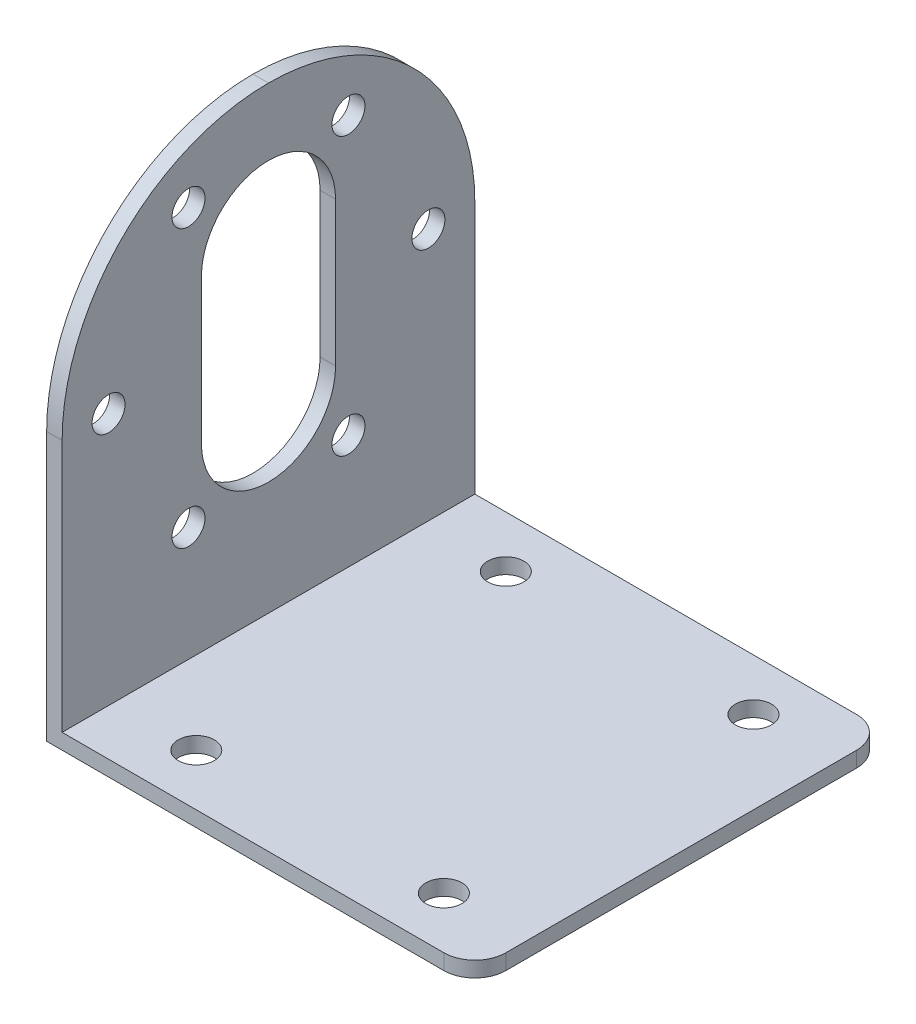
SolidWorks part; units mm, degrees
ref_plane "Front" through (0, 0, 0) normal (0, 0, 1) x (1, 0, 0)
ref_plane "Top" through (0, 0, 0) normal (0, 1, 0) x (1, 0, 0)
ref_plane "Right" through (0, 0, 0) normal (1, 0, 0) x (0, 0, -1)
sketch "草图3" plane through (0, 0, 0) normal (0, 1, 0) x (1, 0, 0)
  line L1 (-20.75, -20) -> (20.75, -20)
  line L2 (-20.75, -20) -> (-20.75, 20)
  line L3 (-20.75, 20) -> (20.75, 20)
  line L4 (20.75, -20) -> (20.75, 20)
  line L5 (-20.75, -20) -> (20.75, 20) construction
  line L6 (-20.75, 20) -> (20.75, -20) construction
  point P0 (0, 0)
  dimension "D1" = 41.5
  dimension "D2" = 40
extrude "凸台-拉伸1" add sketch "草图3" along normal blind 1.5
sketch "草图4" plane through (0, 1.5, 0) normal (0, 1, 0) x (1, 0, 0)
  line L0 (-20.75, -20) -> (20.75, -20) construction
  line L1 (-20.75, 20) -> (-19.25, 20)
  line L2 (-20.75, 20) -> (-20.75, -20)
  line L3 (-20.75, -20) -> (-19.25, -20)
  line L4 (-19.25, 20) -> (-19.25, -20)
  dimension "D1" = 1.5
extrude "凸台-拉伸2" add sketch "草图4" along normal blind 44.5
sketch "草图5" plane through (0, 1.5, 0) normal (0, 1, 0) x (1, 0, 0)
  line L0 (0, 20) -> (0, -20) construction
  line L1 (20.75, 20) -> (-19.25, 20) construction
  line L2 (-19.25, -20) -> (20.75, -20) construction
  line L3 (-19.25, 0) -> (20.75, 0) construction
  line L4 (-19.25, -20) -> (-19.25, 20) construction
  line L5 (20.75, -20) -> (20.75, 20) construction
  circle A0 centre (-11.25, 15) radius 1.75
  circle A1 centre (12.75, 15) radius 1.75
  circle A2 centre (-11.25, -15) radius 1.75
  circle A3 centre (12.75, -15) radius 1.75
  dimension "D1" = 3.5
  dimension "D2" = 3.5
  dimension "D3" = 3.5
  dimension "D4" = 3.5
  dimension "D5" = 15
  dimension "D6" = 15
  dimension "D7" = 15
  dimension "D8" = 15
  dimension "D9" = 8
  dimension "D10" = 8
  dimension "D11" = 24
  dimension "D12" = 24
extrude "切除-拉伸1" cut sketch "草图5" against normal blind 1.5
sketch "草图6" plane through (-19.25, 0, 0) normal (1, 0, 0) x (0, 0, -1)
  line L0 (-20, 26) -> (20, 26) construction
  line L1 (-20, 46) -> (-20, 1.5) construction
  line L2 (20, 46) -> (20, 1.5) construction
  line L3 (-20, 0) -> (20, 0) construction
  line L4 (0, 46) -> (0, 5.2751) construction
  line L5 (-20, 46) -> (20, 46) construction
  line L6 (-6.5, 33) -> (-6.5, 19)
  line L7 (6.5, 33) -> (6.5, 19)
  arc A0 (6.5, 33) -> (-6.5, 33) centre (0, 33) ccw
  arc A1 (-6.5, 19) -> (6.5, 19) centre (0, 19) ccw
  circle A2 centre (-15.5, 26) radius 1.6
  circle A3 centre (-7.75, 39.4234) radius 1.6
  circle A4 centre (7.75, 39.4234) radius 1.6
  circle A5 centre (15.5, 26) radius 1.6
  circle A6 centre (7.75, 12.5766) radius 1.6
  circle A7 centre (-7.75, 12.5766) radius 1.6
  point P23 (0, 26)
  point P35 (0, 26)
  dimension "D2" = 13
  dimension "D3" = 13
  dimension "D6" = 3.2
  dimension "D1" = 26
  dimension "D4" = 7
  dimension "D5" = 7
  dimension "D7" = 15.5
  dimension "D8" = 6
extrude "切除-拉伸2" cut sketch "草图6" against normal blind 1.5
fillet "圆角3" radius 20 2 edges at (-20, 46, -20) (-20, 46, 20)
fillet "圆角4" radius 3 2 edges at (20.75, 0.75, -20) (20.75, 0.75, 20)
